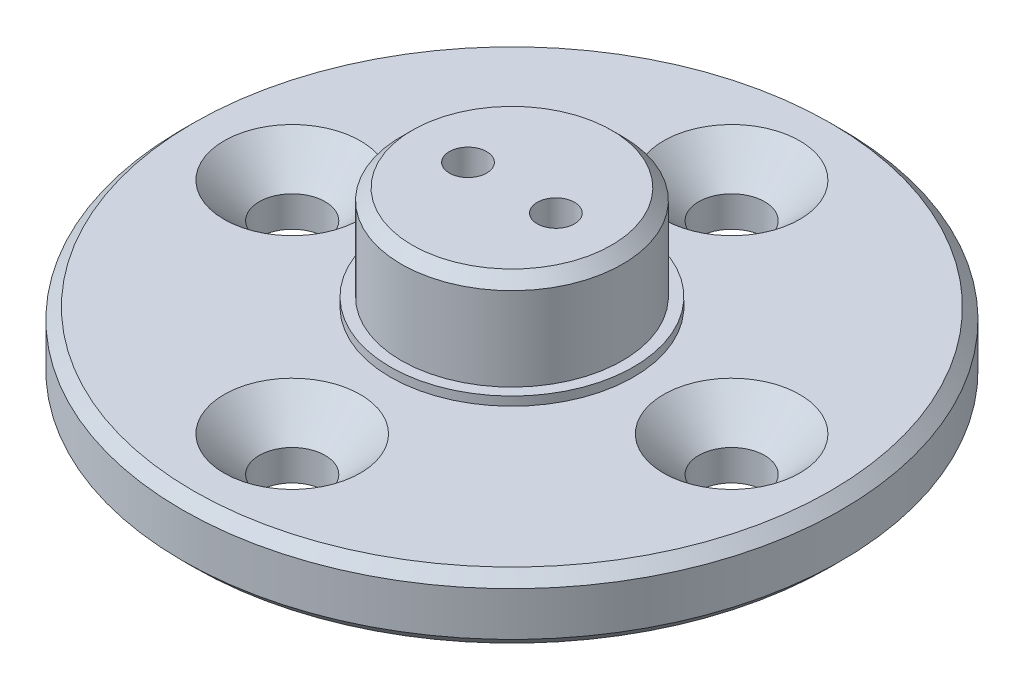
SolidWorks part; units mm, degrees
ref_plane "前视基准面" through (0, 0, 0) normal (0, 0, 1) x (1, 0, 0)
ref_plane "上视基准面" through (0, 0, 0) normal (0, 1, 0) x (1, 0, 0)
ref_plane "右视基准面" through (0, 0, 0) normal (1, 0, 0) x (0, 0, -1)
other "Configuration Table"
sketch "草图1" plane through (0, 0, 0) normal (0, 1, 0) x (1, 0, 0)
  line L0 (-21.98, 0) -> (22.6908, 0) construction
  line L1 (0, 22.7485) -> (0, -21.9381) construction
  circle A0 centre (0, 0) radius 15
  circle A1 centre (0, 10) radius 1.5
  circle A2 centre (10, 0) radius 1.5
  circle A3 centre (0, -10) radius 1.5
  circle A4 centre (-10, 0) radius 1.5
  point P15 (0, 0)
  dimension "D1" = 3
  dimension "D3" = 30
  dimension "D2" = 10
extrude "凸台-拉伸1" add sketch "草图1" along normal blind 3
sketch "草图2" plane through (0, 3, 0) normal (0, 1, 0) x (1, 0, 0)
  line L0 (0, 1.9211) -> (0, -1.7964) construction
  line L1 (-1.959, 0) -> (1.7076, 0) construction
  circle A1 centre (0, 0) radius 5.035
  circle A3 centre (2, 0) radius 0.85
  circle A4 centre (-2, 0) radius 0.85
  dimension "D1" = 10.07
  dimension "D2" = 1.7
  dimension "D3" = 4
extrude "凸台-拉伸2" add sketch "草图2" along normal blind 4.7
sketch "草图4" plane through (0, 3, 0) normal (0, 1, 0) x (1, 0, 0)
  circle A8 centre (0, 0) radius 5.535
  circle A9 centre (0, 0) radius 5.035 construction
  point P15 (0, 0)
  dimension "D1" = 0.5
extrude "凸台-拉伸3" add sketch "草图4" along normal blind 0.4
chamfer "倒角1" distance 0.5 angle 45 1 edges at (0, 7.7, 5.035)
chamfer "倒角3" distance 0.5 angle 45 2 edges at (0, 0, 15) (0, 3, 15)
chamfer "倒角4" distance 1.6 angle 45 4 edges at (10, 3, 1.5) (0, 3, 11.5) (-10, 3, 1.5) (0, 3, -8.5)
